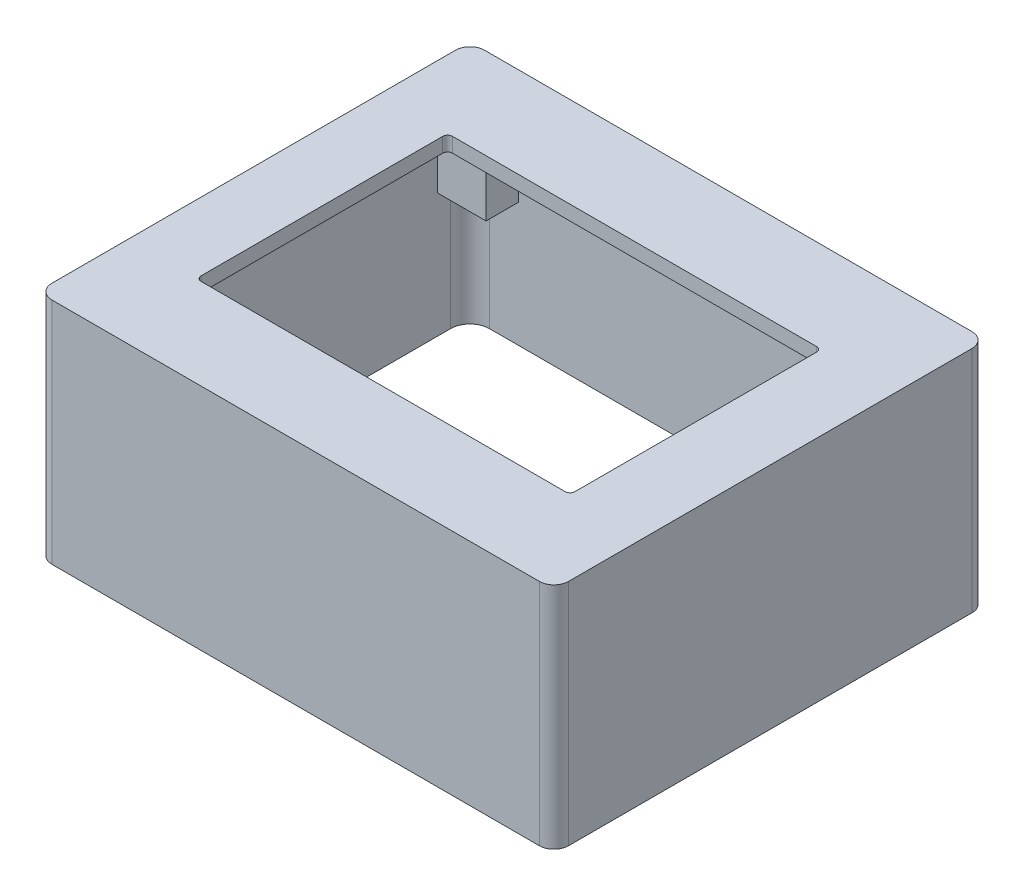
SolidWorks part; units mm, degrees
ref_plane "Front Plane" through (0, 0, 0) normal (0, 0, 1) x (1, 0, 0)
ref_plane "Top Plane" through (0, 0, 0) normal (0, 1, 0) x (1, 0, 0)
ref_plane "Right Plane" through (0, 0, 0) normal (1, 0, 0) x (0, 0, -1)
sketch "Sketch1" plane through (0, 0, 0) normal (0, 1, 0) x (1, 0, 0)
  line L0 (-43.465, 36.8) -> (-43.465, -36.8) construction
  line L1 (49.02, 40.405) -> (-49.02, 40.405)
  line L2 (49.02, 40.405) -> (49.02, -40.405)
  line L3 (49.02, -40.405) -> (-49.02, -40.405)
  line L4 (-49.02, 40.405) -> (-49.02, -40.405)
  line L5 (49.02, 40.405) -> (-49.02, -40.405) construction
  line L6 (49.02, -40.405) -> (-49.02, 40.405) construction
  line L7 (-49.02, 33.2) -> (49.02, 33.2)
  line L8 (-49.02, 33.2) -> (-49.02, -33.2)
  line L9 (-49.02, -33.2) -> (49.02, -33.2)
  line L10 (49.02, 33.2) -> (49.02, -33.2)
  line L11 (-49.02, 33.2) -> (49.02, -33.2) construction
  line L12 (-49.02, -33.2) -> (49.02, 33.2) construction
  line L13 (-39.02, 25.8) -> (37.72, 25.8)
  line L14 (-39.02, 25.8) -> (-39.02, -25.8)
  line L15 (-39.02, -25.8) -> (37.72, -25.8)
  line L16 (37.72, 25.8) -> (37.72, -25.8)
  line L17 (-43.465, -36.8) -> (43.465, -36.8) construction
  line L18 (51.02, 42.405) -> (-51.02, 42.405)
  line L19 (-51.02, 42.405) -> (-51.02, -42.405)
  line L20 (51.02, -42.405) -> (-51.02, -42.405)
  line L21 (51.02, 42.405) -> (51.02, -42.405)
  line L22 (53.02, 44.405) -> (-53.02, 44.405)
  line L23 (-53.02, 44.405) -> (-53.02, -44.405)
  line L24 (53.02, -44.405) -> (-53.02, -44.405)
  line L25 (53.02, 44.405) -> (53.02, -44.405)
  line L26 (-49.02, -33.7) -> (-39.02, -33.7)
  line L27 (-39.02, -33.7) -> (-39.02, -40.405)
  line L28 (0, 0) -> (0, -44.405) construction
  line L29 (0, 0) -> (-53.02, 0) construction
  line L30 (49.02, -33.7) -> (39.02, -33.7)
  line L31 (39.02, -33.7) -> (39.02, -40.405)
  line L32 (49.02, 33.7) -> (39.02, 33.7)
  line L33 (39.02, 33.7) -> (39.02, 40.405)
  line L34 (-39.02, 33.7) -> (-39.02, 40.405)
  line L35 (-49.02, 33.7) -> (-39.02, 33.7)
  circle A0 centre (-43.465, 36.8) radius 1.35
  circle A1 centre (43.465, 36.8) radius 1.35
  circle A2 centre (-43.465, -36.8) radius 1.35
  circle A3 centre (43.465, -36.8) radius 1.35
  point P0 (0, 0)
  point P5 (0, 0)
  point P23 (0, -36.8)
  point P24 (0, -40.405)
  point P25 (-43.465, 0)
  point P26 (-49.02, 0)
  dimension "D8" = 2.7
  dimension "D9" = 2.7
  dimension "D10" = 2.7
  dimension "D11" = 2.7
  dimension "D12" = 86.93
  dimension "D13" = 73.6
  dimension "D16" = 0.5
  dimension "D1" = 80.81
  dimension "D2" = 98.04
  dimension "D3" = 66.4
  dimension "D4" = 11.3
  dimension "D5" = 7.4
  dimension "D6" = 7.4
  dimension "D7" = 10
  dimension "D14" = 2
  dimension "D17" = 10
  dimension "D15" = 2
extrude "Boss-Extrude1" add sketch "Sketch1" against normal blind 3 contours L24 L23 L22 L25 | L15 L16 L13 L14
extrude "Boss-Extrude2" add sketch "Sketch1<3>" against normal blind 19.5 contours L27 L26 L4 L3 A2 | L30 L31 L3 L2 A3 | L33 L32 L2 L1 A1 | L4 L35 L34 L1 A0 region at (48.8996, 0, -37.0525) region at (-39.1404, 0, -37.0525) region at (48.8996, 0, 37.0525) region at (-44.02, 0, 33.8204)
sketch "Sketch1<3>" plane through (0, 0, 0) normal (0, 1, 0) x (1, 0, 0) same geometry as "Sketch1"
extrude "Boss-Extrude3" add sketch "Sketch1<4>" against normal blind 47 contours L25 L22 L23 L24 L18 L21 L20 L19 region at (51.6368, 0, 0)
sketch "Sketch1<4>" plane through (0, 0, 0) normal (0, 1, 0) x (1, 0, 0) same geometry as "Sketch1"
sketch "Sketch2" plane through (0, -3, 0) normal (0, -1, 0) x (1, 0, 0)
  line L0 (-39.02, -25.8) -> (-39.02, 25.8) construction
  line L1 (-38.52, 27.8) -> (37.22, 27.8) construction
  line L2 (-41.02, 25.3) -> (-41.02, -25.3) construction
  line L3 (-38.52, -27.8) -> (37.22, -27.8) construction
  line L4 (39.72, 25.3) -> (39.72, -25.3) construction
  line L5 (-39.02, 25.8) -> (37.72, 25.8) construction
  line L6 (37.72, -25.8) -> (37.72, 25.8) construction
  line L7 (-39.02, -25.8) -> (37.72, -25.8) construction
  line L8 (-38.52, 28.8) -> (37.22, 28.8)
  line L9 (40.72, 25.3) -> (40.72, -25.3)
  line L10 (-38.52, -28.8) -> (37.22, -28.8)
  line L11 (-42.02, 25.3) -> (-42.02, -25.3)
  line L12 (-38.52, 26.8) -> (37.22, 26.8)
  line L13 (38.72, 25.3) -> (38.72, -25.3)
  line L14 (-38.52, -26.8) -> (37.22, -26.8)
  line L15 (-40.02, 25.3) -> (-40.02, -25.3)
  arc A0 (-41.02, -25.3) -> (-38.52, -27.8) centre (-38.52, -25.3) ccw construction
  arc A1 (37.22, -27.8) -> (39.72, -25.3) centre (37.22, -25.3) ccw construction
  arc A2 (37.22, 27.8) -> (39.72, 25.3) centre (37.22, 25.3) cw construction
  arc A3 (-38.52, 27.8) -> (-41.02, 25.3) centre (-38.52, 25.3) ccw construction
  arc A4 (37.22, 28.8) -> (40.72, 25.3) centre (37.22, 25.3) cw
  arc A5 (37.22, -28.8) -> (40.72, -25.3) centre (37.22, -25.3) ccw
  arc A6 (-42.02, -25.3) -> (-38.52, -28.8) centre (-38.52, -25.3) ccw
  arc A7 (-38.52, 28.8) -> (-42.02, 25.3) centre (-38.52, 25.3) ccw
  arc A8 (37.22, 26.8) -> (38.72, 25.3) centre (37.22, 25.3) cw
  arc A9 (37.22, -26.8) -> (38.72, -25.3) centre (37.22, -25.3) ccw
  arc A10 (-40.02, -25.3) -> (-38.52, -26.8) centre (-38.52, -25.3) ccw
  arc A11 (-38.52, 26.8) -> (-40.02, 25.3) centre (-38.52, 25.3) ccw
  dimension "D5" = 2.5
  dimension "D1" = 2
  dimension "D2" = 2
  dimension "D3" = 2
  dimension "D4" = 2
  dimension "D6" = 1
  dimension "D7" = 1
extrude "Cut-Extrude1" [suppressed] cut sketch "Sketch2" against normal blind 1.5
fillet "Fillet1" radius 4 4 edges at (51.02, -25, -42.405) (-51.02, -25, -42.405) (51.02, -25, 42.405) (-51.02, -25, 42.405)
fillet "Fillet2" radius 3 4 edges at (-53.02, -23.5, 44.405) (53.02, -23.5, 44.405) (53.02, -23.5, -44.405) (-53.02, -23.5, -44.405)
fillet "Fillet3" radius 1 4 edges at (-39.02, -1.5, 25.8) (37.72, -1.5, 25.8) (37.72, -1.5, -25.8) (-39.02, -1.5, -25.8)
sketch "Sketch3" plane through (0, 0, -44.405) normal (0, 0, -1) x (-1, 0, 0)
  line L1 (-26.52, -30.5) -> (-12.52, -30.5)
  line L2 (-26.52, -30.5) -> (-26.52, -38.5)
  line L3 (-26.52, -38.5) -> (-12.52, -38.5)
  line L4 (-12.52, -30.5) -> (-12.52, -38.5)
  line L5 (47.02, -3) -> (-47.02, -3) construction
  line L6 (-47.02, -47) -> (-47.02, -3) construction
  dimension "D1" = 8
  dimension "D2" = 14
  dimension "D3" = 20.5
  dimension "D4" = 27.5
extrude "Cut-Extrude2" cut sketch "Sketch3" against normal up to next
